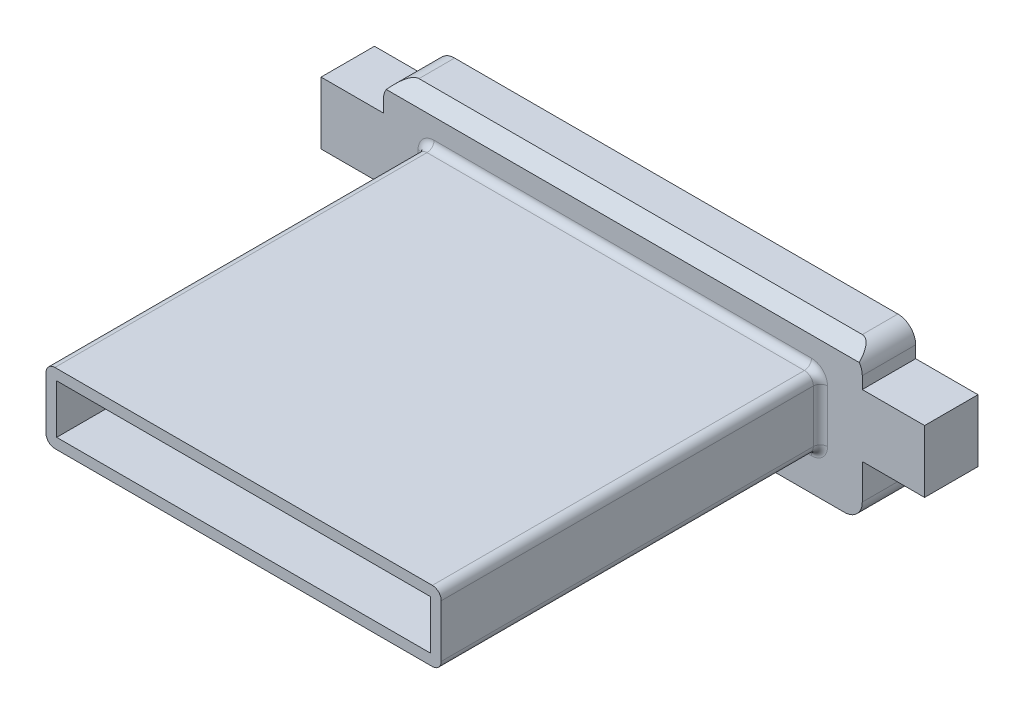
SolidWorks part; units mm, degrees
ref_plane "Front Plane" through (0, 0, 0) normal (0, 0, 1) x (1, 0, 0)
ref_plane "Top Plane" through (0, 0, 0) normal (0, 1, 0) x (1, 0, 0)
ref_plane "Right Plane" through (0, 0, 0) normal (1, 0, 0) x (0, 0, -1)
sketch "Sketch1" plane through (0, 0, 0) normal (0, 0, 1) x (1, 0, 0)
  line L0 (0, 20.5563) -> (0, -8) construction
  line L1 (-28.8085, 0) -> (32.7718, 0) construction
  line L3 (26.9, 8.4) -> (-26.9, 8.4)
  line L4 (26.9, 8.4) -> (26.9, -8.4)
  line L5 (26.9, -8.4) -> (-26.9, -8.4)
  line L6 (-26.9, 8.4) -> (-26.9, -8.4)
  line L7 (26.9, 8.4) -> (-26.9, -8.4) construction
  line L8 (26.9, -8.4) -> (-26.9, 8.4) construction
  line L12 (-21, 2.75) -> (-21, -2.75)
  line L17 (-21, -2.75) -> (21, -2.75)
  line L18 (21, -2.75) -> (21, 2.75)
  line L19 (21, 2.75) -> (-21, 2.75)
  point P5 (0, 0)
  point P10 (0, 0)
  point P13 (0, 2.75)
  point P16 (21, 0)
  dimension "D1" = 16.8
  dimension "D2" = 42
  dimension "D3" = 5.9
  dimension "D4" = 5.5
  dimension "D5" = 53.8
extrude "Boss-Extrude1" add sketch "Sketch1" along normal mid plane 54
sketch "Sketch4" plane through (0, 0, 0) normal (0, 0, 1) x (1, 0, 0)
  line L0 (21, -2.75) -> (21, 2.75) construction
  line L1 (-21, -2.75) -> (21, -2.75) construction
  line L2 (-21, 2.75) -> (-21, -2.75) construction
  line L3 (21, 2.75) -> (-21, 2.75) construction
  line L4 (21, -2.75) -> (21, 2.75) construction
  line L5 (-21, -2.75) -> (21, -2.75) construction
  line L6 (-21, 2.75) -> (-21, -2.75) construction
  line L7 (21, 2.75) -> (-21, 2.75) construction
  line L8 (22.2, -3.95) -> (22.2, 3.95)
  line L9 (22.2, 3.95) -> (-22.2, 3.95)
  line L10 (-22.2, 3.95) -> (-22.2, -3.95)
  line L11 (-22.2, -3.95) -> (22.2, -3.95)
  line L12 (-26.9, -8.4) -> (26.9, -8.4) construction
  line L13 (26.9, -8.4) -> (26.9, 8.4) construction
  line L14 (26.9, 8.4) -> (-26.9, 8.4) construction
  line L15 (-26.9, 8.4) -> (-26.9, -8.4) construction
  line L16 (-26.9, -8.4) -> (26.9, -8.4)
  line L17 (26.9, -8.4) -> (26.9, 8.4)
  line L18 (26.9, 8.4) -> (-26.9, 8.4)
  line L19 (-26.9, 8.4) -> (-26.9, -8.4)
  dimension "D1" = 1.2
extrude "Cut-Extrude2" cut sketch "Sketch4" against normal mid plane 38.7
sketch "Sketch2" plane through (0, 0, 19.35) normal (0, 0, -1) x (-1, 0, 0)
  line L0 (0, 12.8087) -> (0, -16.4683) construction
  line L1 (21, -2.75) -> (-21, -2.75) construction
  line L3 (-26.9, -2.45) -> (-26.9, 7.55)
  line L6 (-26.9, -2.45) -> (-33.9, -2.45)
  line L7 (-26.9, -2.45) -> (-26.9, 7.55)
  line L8 (-26.9, 7.55) -> (-33.9, 7.55)
  line L9 (-33.9, -2.45) -> (-33.9, 7.55)
  line L13 (-26.9, -8.4) -> (-26.9, 8.4) construction
  line L16 (33.9, -2.45) -> (33.9, 7.55)
  line L17 (26.9, 7.55) -> (33.9, 7.55)
  line L18 (26.9, -2.45) -> (26.9, 7.55)
  line L19 (26.9, -2.45) -> (33.9, -2.45)
  line L20 (26.9, -2.45) -> (26.9, 7.55)
  dimension "D1" = 7
  dimension "D2" = 10
  dimension "D3" = 0.3
extrude "Boss-Extrude2" add sketch "Sketch2" against normal blind 6 contours L9 L6 L3 L8 | L17 L18 L19 L16
sketch "Sketch3" plane through (0, -2.45, 0) normal (0, -1, 0) x (1, 0, 0)
  line L0 (0, 34.141) -> (0, 0) construction
  line L1 (-26.9, 25.35) -> (-26.9, 19.35) construction
  line L4 (-33.9, 19.35) -> (-33.9, 25.35) construction
  circle A0 centre (-30.9, 22.35) radius 1.35
  circle A2 centre (30.9, 22.35) radius 1.35
  point P10 (-33.9, 22.35)
  dimension "D1" = 2.7
  dimension "D2" = 4
extrude "Cut-Extrude1" cut sketch "Sketch3" against normal blind 8 contours A0 | A2
mirror "Mirror8" about plane through (0, 0, 0) normal (0, 0, 1) of "Cut-Extrude1", "Boss-Extrude2"
sketch "Sketch7" plane through (0, 0, -27) normal (0, 0, -1) x (-1, 0, 0)
  line L0 (26.9, 8.4) -> (26.9, -8.4) construction
  line L1 (-26.9, 8.4) -> (26.9, 8.4)
  line L2 (-26.9, 8.4) -> (-26.9, 7.9)
  line L3 (-26.9, 7.9) -> (26.9, 7.9)
  line L4 (26.9, 8.4) -> (26.9, 7.9)
  dimension "D1" = 0.5
extrude "Cut-Extrude4" cut sketch "Sketch7" against normal up to next
fillet "Fillet2" radius 1 4 edges at (-22.2, -3.95, 0) (22.2, -3.95, 0) (22.2, 3.95, 0) (-22.2, 3.95, 0)
fillet "Filete1" radius 2 8 edges at (-26.9, -8.4, -23.175) (26.9, -8.4, -23.175) (26.9, -8.4, 23.175) (-26.9, -8.4, 23.175) (26.9, 8.4, 23.175) (-26.9, 8.4, 23.175) (-26.9, 7.9, -23.175) (26.9, 7.9, -23.175)
sketch "Sketch5" plane through (0, 0, 27) normal (0, 0, 1) x (1, 0, 0)
  line L0 (24.9, 8.4) -> (-24.9, 8.4) construction
  line L1 (-26.9, -8.4) -> (26.9, -8.4)
  line L2 (-26.9, -8.4) -> (-26.9, 8.4)
  line L3 (-26.9, 8.4) -> (26.9, 8.4)
  line L4 (26.9, -8.4) -> (26.9, 8.4)
  line L5 (-26.9, -8.4) -> (26.9, 8.4) construction
  line L6 (-26.9, 8.4) -> (26.9, -8.4) construction
  line L7 (-26.9, 6.4) -> (-26.9, -6.4) construction
  point P0 (0, 0)
extrude "Cut-Extrude3" cut sketch "Sketch5" against normal up to surface (1.65 mm away) up to face at (29.645, 3.3256, 25.35)
chamfer "Chamfer1" distance 2 angle 24 1 edges at (0, 7.9, -19.35) first distance on face at (0, 7.9, -23.175)
sketch "Sketch8" plane through (0, 0, -25.35) normal (0, 0, -1) x (-1, 0, 0)
  line L0 (-26.0303, 7.55) -> (-33.9, 7.55)
  line L1 (-33.9, 7.55) -> (-33.9, 4.55)
  line L2 (-33.9, -2.45) -> (-33.9, 7.55) construction
  line L3 (-33.9, 4.55) -> (-26.9, 4.55)
  line L4 (-26.9, -6.4) -> (-26.9, 5.9) construction
  line L5 (-26.9, 4.55) -> (-26.9, 5.9)
  line L6 (-26.9, -2.45) -> (-33.9, -2.45) construction
  line L7 (0, 0) -> (0, 22.4575) construction
  line L8 (26.9, 4.55) -> (26.9, 5.9)
  line L9 (33.9, 4.55) -> (26.9, 4.55)
  line L10 (33.9, 7.55) -> (33.9, 4.55)
  line L11 (26.0303, 7.55) -> (33.9, 7.55)
  arc A0 (-24.9, 7.9) -> (-26.9, 5.9) centre (-24.9, 5.9) ccw construction
  arc A1 (-26.0303, 7.55) -> (-26.9, 5.9) centre (-24.9, 5.9) ccw
  arc A2 (26.0303, 7.55) -> (26.9, 5.9) centre (24.9, 5.9) cw
  dimension "D1" = 7
extrude "Cut-Extrude5" cut sketch "Sketch8" against normal up to next
sketch "Sketch9" plane through (0, 0, 25.35) normal (0, 0, 1) x (1, 0, 0)
  line L0 (26.9, 5.9) -> (26.9, 7.55)
  line L1 (0, 0) -> (0, 14.9997) construction
  line L2 (-26.9, 5.9) -> (-26.9, 4.55)
  line L3 (-26.9, 4.55) -> (-33.9, 4.55)
  line L4 (33.9, 7.55) -> (26.0303, 7.55)
  line L5 (33.9, 4.55) -> (33.9, 7.55)
  line L6 (26.9, 4.55) -> (33.9, 4.55)
  line L7 (26.9, 5.9) -> (26.9, 4.55)
  line L8 (33.9, 7.55) -> (26.9, 7.55)
  line L9 (33.9, 4.55) -> (33.9, 7.55)
  line L10 (26.9, 4.55) -> (33.9, 4.55)
  line L11 (26.9, 5.9) -> (26.9, 4.55)
  line L12 (-33.9, 4.55) -> (-33.9, 7.55)
  line L13 (-33.9, 7.55) -> (-26.9, 7.55)
  line L14 (-26.9, 5.9) -> (-26.9, 7.55)
  arc A1 (26.9, 5.9) -> (26.0303, 7.55) centre (24.9, 5.9) ccw
  dimension "D1" = 0
extrude "Cut-Extrude6" cut sketch "Sketch9" against normal up to next
sketch "Sketch10" plane through (0, 4.55, 0) normal (0, 1, 0) x (1, 0, 0)
  circle A1 centre (30.9, -22.35) radius 1.35
  circle A2 centre (30.9, -22.35) radius 1.35
  circle A3 centre (-30.9, -22.35) radius 1.35
  circle A4 centre (-30.9, -22.35) radius 1.35
  dimension "D1" = 0
  dimension "D2" = 0
extrude "Boss-Extrude3" add sketch "Sketch10" against normal up to surface (7 mm away) up to face at (-29.55, -2.45, 22.35)
mirror "Mirror9" about plane through (0, 0, 0) normal (0, 0, 1) of "Boss-Extrude3"
sketch "Sketch11" plane through (0, 0, -27) normal (0, 0, -1) x (-1, 0, 0)
  line L4 (26.9, -6.4) -> (26.9, 5.9)
  line L5 (24.9, 7.9) -> (-24.9, 7.9)
  line L6 (-26.9, 5.9) -> (-26.9, -6.4)
  line L7 (-24.9, -8.4) -> (24.9, -8.4)
  line L8 (26.9, -6.4) -> (26.9, 5.9)
  line L9 (24.9, 7.9) -> (-24.9, 7.9)
  line L10 (-26.9, 5.9) -> (-26.9, -6.4)
  line L11 (-24.9, -8.4) -> (24.9, -8.4)
  arc A4 (26.9, 5.9) -> (24.9, 7.9) centre (24.9, 5.9) ccw
  arc A5 (-24.9, 7.9) -> (-26.9, 5.9) centre (-24.9, 5.9) ccw
  arc A6 (-26.9, -6.4) -> (-24.9, -8.4) centre (-24.9, -6.4) ccw
  arc A7 (24.9, -8.4) -> (26.9, -6.4) centre (24.9, -6.4) ccw
  arc A8 (26.9, 5.9) -> (24.9, 7.9) centre (24.9, 5.9) ccw
  arc A9 (-24.9, 7.9) -> (-26.9, 5.9) centre (-24.9, 5.9) ccw
  arc A10 (-26.9, -6.4) -> (-24.9, -8.4) centre (-24.9, -6.4) ccw
  arc A11 (24.9, -8.4) -> (26.9, -6.4) centre (24.9, -6.4) ccw
  dimension "D1" = 0
extrude "Cut-Extrude7" cut sketch "Sketch11" against normal up to surface (1.65 mm away) up to face at (-30.4, 1.05, -25.35)
sketch "Sketch13" plane through (-33.9, 0, 0) normal (-1, 0, 0) x (0, 0, 1)
  line L1 (19.35, -8.4) -> (25.35, -8.4)
  line L2 (19.35, -8.4) -> (19.35, 8.4)
  line L3 (19.35, 8.4) -> (25.35, 8.4)
  line L4 (25.35, -8.4) -> (25.35, 8.4)
extrude "Cut-Extrude8" cut sketch "Sketch13" against normal through all
fillet "Fillet6" radius 0.8 8 edges at (-21.9071, -3.6571, -19.35) (-22.2, 0, -19.35) (-21.9071, 3.6571, -19.35) (0, 3.95, -19.35) (21.9071, 3.6571, -19.35) (22.2, 0, -19.35) (21.9071, -3.6571, -19.35) (0, -3.95, -19.35)
sketch "Sketch14" plane through (0, 0, 19.35) normal (0, 0, 1) x (1, 0, 0)
  line L0 (22.2, -2.95) -> (22.2, 2.95) construction
  line L1 (-21.2, -3.95) -> (21.2, -3.95) construction
  line L2 (-22.2, 2.95) -> (-22.2, -2.95) construction
  line L3 (21.2, 3.95) -> (-21.2, 3.95) construction
  line L4 (22.2, -2.95) -> (22.2, 2.95)
  line L5 (-21.2, -3.95) -> (21.2, -3.95)
  line L6 (-22.2, 2.95) -> (-22.2, -2.95)
  line L7 (21.2, 3.95) -> (-21.2, 3.95)
  line L8 (21, 2.75) -> (21, -2.75) construction
  line L9 (21, -2.75) -> (-21, -2.75) construction
  line L10 (-21, -2.75) -> (-21, 2.75) construction
  line L11 (-21, 2.75) -> (21, 2.75) construction
  line L12 (21, 2.75) -> (21, -2.75)
  line L13 (21, -2.75) -> (-21, -2.75)
  line L14 (-21, -2.75) -> (-21, 2.75)
  line L15 (-21, 2.75) -> (21, 2.75)
  arc A0 (22.2, 2.95) -> (21.2, 3.95) centre (21.2, 2.95) ccw construction
  arc A1 (21.2, -3.95) -> (22.2, -2.95) centre (21.2, -2.95) ccw construction
  arc A2 (-22.2, -2.95) -> (-21.2, -3.95) centre (-21.2, -2.95) ccw construction
  arc A3 (-21.2, 3.95) -> (-22.2, 2.95) centre (-21.2, 2.95) ccw construction
  arc A4 (22.2, 2.95) -> (21.2, 3.95) centre (21.2, 2.95) ccw
  arc A5 (21.2, -3.95) -> (22.2, -2.95) centre (21.2, -2.95) ccw
  arc A6 (-22.2, -2.95) -> (-21.2, -3.95) centre (-21.2, -2.95) ccw
  arc A7 (-21.2, 3.95) -> (-22.2, 2.95) centre (-21.2, 2.95) ccw
extrude "Boss-Extrude4" add sketch "Sketch14" along normal blind 3.9
